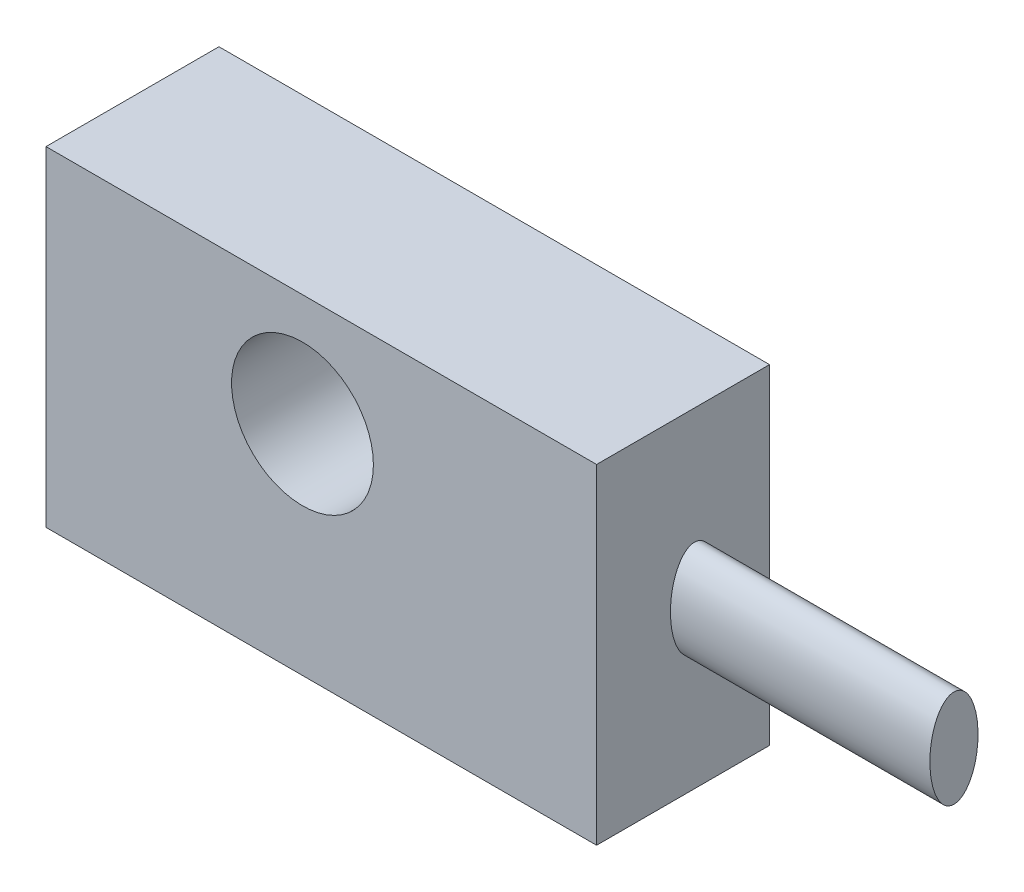
SolidWorks part; units mm, degrees
material "Al-Aly 7075-T7351 Plate per AMS 4078"
ref_plane "Z Plane" through (0, 0, 0) normal (0, 0, 1) x (1, 0, 0)
ref_plane "Y Plane" through (0, 0, 0) normal (0, 1, 0) x (1, 0, 0)
ref_plane "X Plane" through (0, 0, 0) normal (1, 0, 0) x (0, 0, -1)
ref_axis "X Axis" through (-88.99, 0, 0) along (1, 0, 0)
ref_axis "Z Axis" through (0, 0, -88.99) along (0, 0, 1)
ref_axis "Y Axis" through (0, 55, 0) along (0, -1, 0)
sketch "Sketch1" plane through (0, 0, 0) normal (0, 0, 1) x (1, 0, 0)
  line L1 (-80.8622, -48.4364) -> (80.8622, -48.4364)
  line L2 (-80.8622, -48.4364) -> (-80.8622, 48.4364)
  line L3 (-80.8622, 48.4364) -> (80.8622, 48.4364)
  line L4 (80.8622, -48.4364) -> (80.8622, 48.4364)
  line L5 (-80.8622, -48.4364) -> (80.8622, 48.4364) construction
  line L6 (-80.8622, 48.4364) -> (80.8622, -48.4364) construction
  point P0 (0, 0)
extrude "Boss-Extrude1" add sketch "Sketch1" along normal blind 50.8
sketch "Sketch2" plane through (0, 0, 50.8) normal (0, 0, 1) x (1, 0, 0)
  circle A0 centre (-5.5257, 15.5605) radius 20.831
extrude "Cut-Extrude1" cut sketch "Sketch2" against normal through all contours A0
sketch "Sketch3" plane through (80.8622, 0, 0) normal (1, 0, 0) x (0, 0, -1)
  ellipse E0 centre (-22.0345, 0) end of major axis (-22.0345, -14.2941) minor radius 7.0747
extrude "Boss-Extrude2" add sketch "Sketch3" along normal blind 76.2
